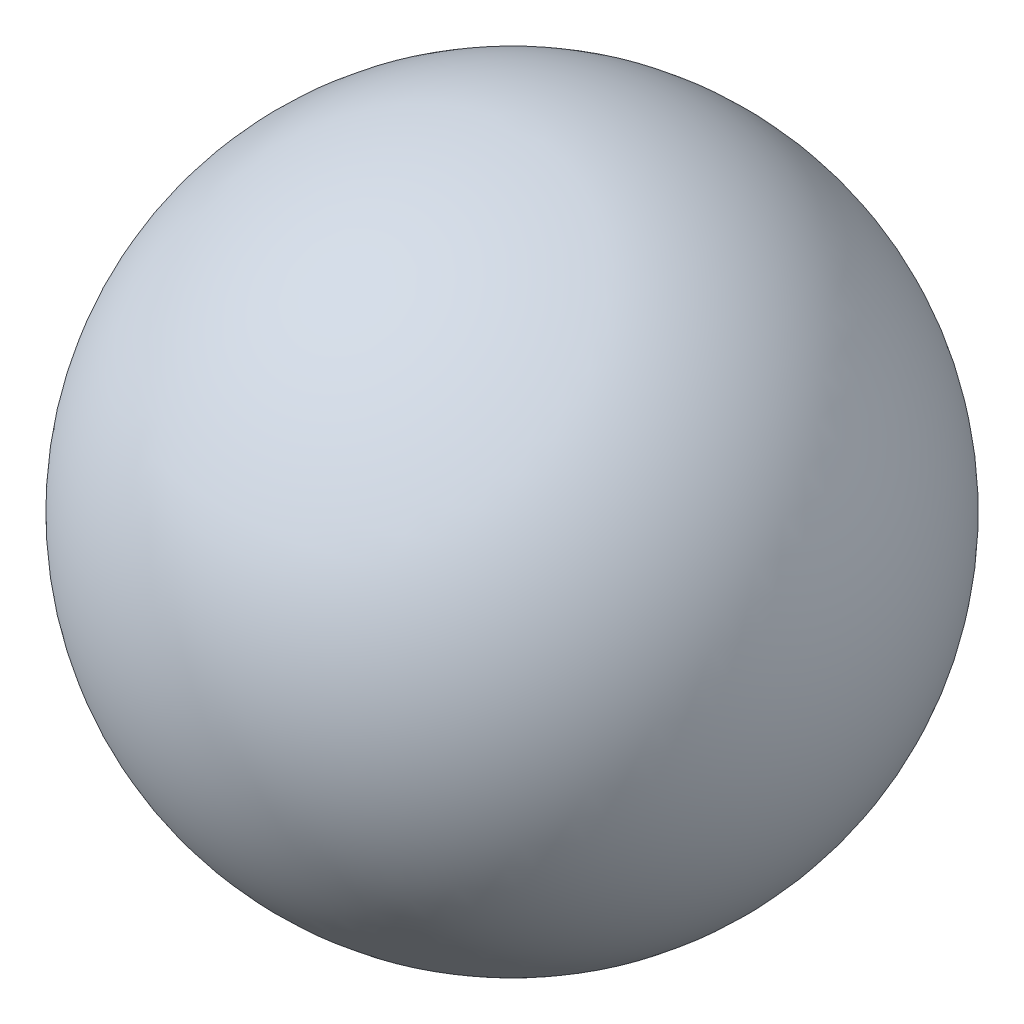
SolidWorks part; units mm, degrees
note: '?' marks a value the reader was unsure of.
material "Silicon nitride"
ref_plane "Front Plane" through (0, 0, 0) normal (0, 0, 1) x (1, 0, 0)
ref_plane "Top Plane" through (0, 0, 0) normal (0, 1, 0) x (1, 0, 0)
ref_plane "Right Plane" through (0, 0, 0) normal (1, 0, 0) x (0, 0, -1)
ref_axis "Centre Axis" through (0, 3.9291, 0) along (0, -1, 0)
ref_axis "Revolution Axis" through (0, 0, 3.9291) along (0, 0, -1)?
sketch "Sketch1" plane through (0, 0, 0) normal (0, 0, 1) x (1, 0, 0)
  line L0 (0, 3.5719) -> (0, -3.5719)
  line L2 (55, 0) -> (-55, 0) construction
  line L3 (0, 3.9291) -> (0, -3.9291) construction
  arc A0 (0, 3.5719) -> (0, -3.5719) centre (0, 0) ccw
  arc A1 (0, -3.5719) -> (0, 3.5719) centre (0, 0) ccw construction
  dimension "D1" = 7.1437
revolve "Revolve1" add sketch "Sketch1" angle 360 about axis through (0, 3.9291, 0) along (0, -1, 0)
